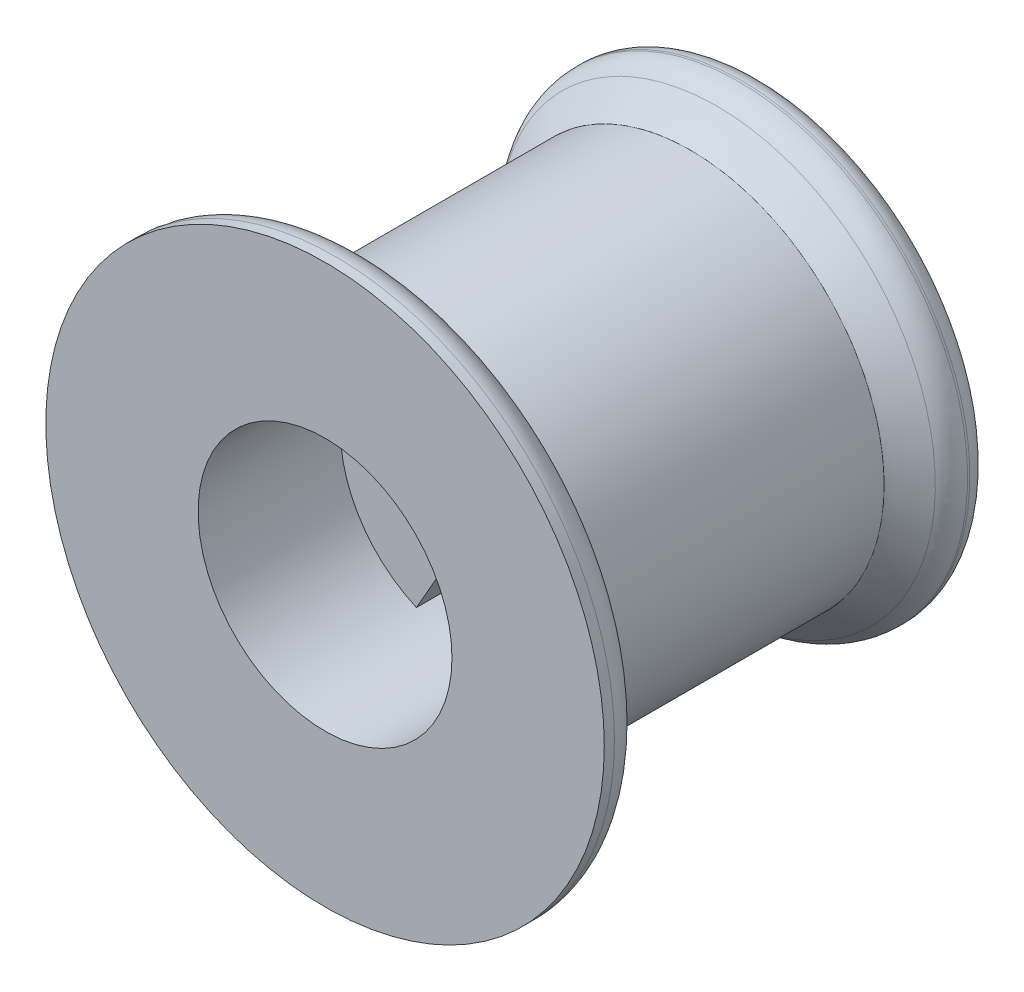
SolidWorks part; units mm, degrees
note: The reader was unsure of these and kept them because the rebuilt part matched: shared geometry of "Sketch2<6>".
ref_plane "Front Plane" through (0, 0, 0) normal (0, 0, 1) x (1, 0, 0)
ref_plane "Top Plane" through (0, 0, 0) normal (0, 1, 0) x (1, 0, 0)
ref_plane "Right Plane" through (0, 0, 0) normal (1, 0, 0) x (0, 0, -1)
sketch "Sketch2" plane through (0, 0, 0) normal (0, 0, 1) x (1, 0, 0)
  line L0 (0, 12.5) -> (0, -12.5) construction
  line L1 (-30.417, 0) -> (37.5234, 0) construction
  line L6 (0, 5.5) -> (0, 8.5) construction
  line L7 (5, -11.4564) -> (2, -6.1847)
  line L8 (-5, -11.4564) -> (-2, -6.1847)
  line L9 (-5, 11.4564) -> (-2, 6.1847)
  line L14 (0, 7.5) -> (0, 17.5) construction
  line L16 (5, 11.4564) -> (2, 6.1847)
  circle A0 centre (0, 0) radius 19.05
  circle A1 centre (0, 0) radius 12.5
  circle A2 centre (0, 0) radius 6.5
  circle A3 centre (0, 0) radius 27.5
  point P7 (0, 6.5)
  dimension "D1" = 38.1
  dimension "D2" = 25
  dimension "D3" = 13
  dimension "D6" = 55
  dimension "D4" = 4
  dimension "D5" = 10
extrude "Boss-Extrude1" add sketch "Sketch2" against normal blind 10.8 contours A2 L9 A1 L8 | A2 L7 A1 L16
extrude "Boss-Extrude3" add sketch "Sketch2<6>" along normal blind 10 separate body contours A0 A1 | A2
sketch "Sketch2<6>" plane through (0, 0, 0) normal (0, 0, 1) x (1, 0, 0) same geometry as "Sketch2"
sketch "Sketch4" plane through (0, 0, 10) normal (0, 0, 1) x (1, 0, 0)
  circle A0 centre (0, 0) radius 12.5
  circle A1 centre (0, 0) radius 27.5
  dimension "D1" = 55
extrude "Boss-Extrude4" add sketch "Sketch4" along normal blind 4
sketch "Sketch5" plane through (0, 0, 0) normal (0, 0, -1) x (-1, 0, 0)
  circle A0 centre (0, 0) radius 19.05
  circle A1 centre (0, 0) radius 12.5
extrude "Boss-Extrude5" add sketch "Sketch5" along normal up to surface (10.8 mm away) up to face at (-6.5, 0, -10.8)
sketch "Sketch6" plane through (0, 0, -10.8) normal (0, 0, -1) x (-1, 0, 0)
  circle A0 centre (0, 0) radius 19.05
extrude "Boss-Extrude6" add sketch "Sketch6" along normal blind 14.2
sketch "Sketch7" plane through (0, 0, -25) normal (0, 0, -1) x (-1, 0, 0)
  circle A0 centre (0, 0) radius 22.5
  dimension "D1" = 45
extrude "Boss-Extrude7" add sketch "Sketch7" along normal blind 4
fillet "Fillet1" radius 3 1 edges at (27.5, 0, 10)
fillet "Fillet2" radius 3 1 edges at (-19.05, 0, -25)
fillet "Fillet3" radius 3 2 edges at (-22.5, 0, -25)
fillet "Fillet5" radius 2 1 edges at (-22.5, 0, -29)
fillet "Fillet6" radius 4 1 edges at (19.05, 0, 10)
